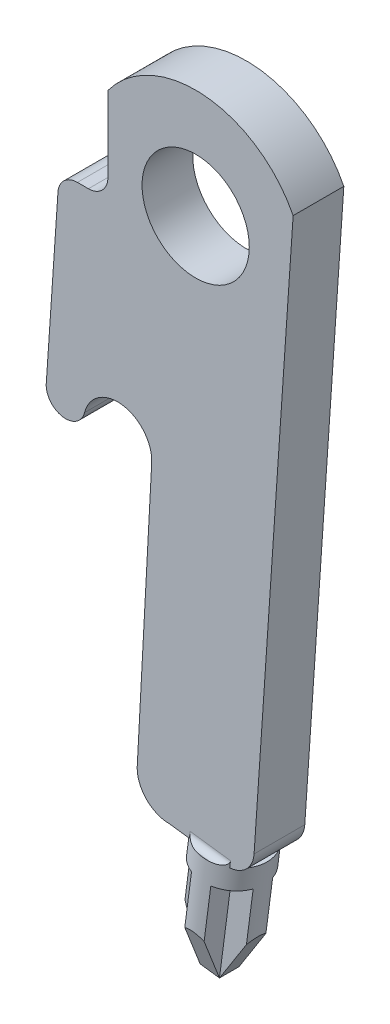
SolidWorks part; units mm, degrees
material "Plain Carbon Steel"
ref_plane "Front Plane" through (0, 0, 0) normal (0, 0, 1) x (1, 0, 0)
ref_plane "Top Plane" through (0, 0, 0) normal (0, 1, 0) x (1, 0, 0)
ref_plane "Right Plane" through (0, 0, 0) normal (1, 0, 0) x (0, 0, -1)
sketch "Sketch1" plane through (0, 0, 0) normal (0, 0, 1) x (1, 0, 0)
  line L0 (16.0633, 36.1424) -> (80.3164, 36.1424) construction
  line L1 (45.7601, 50.3266) -> (45.7601, 46.6183)
  line L2 (45.7601, 46.6183) -> (43.8567, 46.6183)
  line L3 (43.8567, 46.6183) -> (43.3471, 39.1507)
  line L5 (52.9991, 49.7084) -> (51.4727, 27.3397)
  line L6 (47.4717, 38.5713) -> (46.9031, 27.9747)
  line L7 (48.1731, 26.7047) -> (50.1212, 26.4507)
  arc A0 (45.7601, 50.3266) -> (52.9991, 49.7084) centre (49.1891, 47.7867) cw
  arc A1 (43.3471, 39.1507) -> (44.8484, 38.9659) centre (44.1091, 39.1507) ccw
  arc A2 (44.8484, 38.9659) -> (47.4717, 38.5713) centre (46.1411, 38.6427) cw
  circle A5 centre (49.1891, 47.7867) radius 2.0955
  arc A7 (46.9031, 27.9747) -> (48.1731, 26.7047) centre (48.1731, 27.9747) ccw
  arc A8 (51.4727, 27.3397) -> (50.1212, 26.4507) centre (50.4591, 27.4089) cw
  point P10 (0, 0)
  point P19 (42.8058, 39.4047)
  point P22 (0, 0)
  point P23 (44.2839, 38.9493)
  point P24 (0, 0)
  point P25 (0, 0)
  point P26 (44.2626, 39.2936)
  point P27 (0, 0)
  point P28 (0, 0)
  point P29 (44.2905, 39.0006)
  point P30 (49.1891, 47.7867)
  point P31 (0, 0)
  point P32 (0, 0)
  point P33 (0, 0)
  point P34 (0, 0)
  point P35 (0, 0)
  point P36 (0, 0)
  point P37 (0, 0)
  point P38 (0, 0)
  point P39 (0, 0)
  point P40 (0, 0)
  point P41 (0, 0)
  point P42 (0, 0)
  point P43 (0, 0)
  point P44 (0, 0)
  point P45 (0, 0)
  point P46 (0, 0)
  point P47 (0, 0)
  point P48 (0, 0)
  dimension "D1" = 4.191
  dimension "D2" = 4.2672
  dimension "D5" = 8.636
  dimension "D6" = 5.08
  dimension "D8" = 3.048
  dimension "D9" = 0.762
  dimension "D13" = 1.016
  dimension "D17" = 20.447
  dimension "D10" = 19.812
  dimension "D12" = 20.3778
  dimension "D14" = 1.016
  dimension "D15" = 1.27
  dimension "D3" = 1.1684
  dimension "D4" = 3.429
  dimension "D7" = 9.144
  dimension "D11" = 1.27
  dimension "D16" = 21.082
  dimension "D18" = 21.336
extrude "Boss-Extrude1" add sketch "Sketch1" along normal blind 1.9812
fillet "Fillet1" radius 0.762 2 edges at (45.7601, 46.6183, 0.9906) (43.8567, 46.6183, 0.9906)
sketch "Sketch3" plane through (4.2289, 32.4343, 0) normal (-0.1293, -0.9916, 0) x (0.9916, -0.1293, 0)
  line L0 (44.6222, 1.9812) -> (47.1548, 0) construction
  line L1 (47.1548, 1.9812) -> (44.6222, 0) construction
  circle A1 centre (45.8885, 0.9906) radius 1.27
extrude "Boss-Extrude2" add sketch "Sketch3" along normal blind 4.6355
sketch "Sketch5" plane through (3.6296, 27.8377, 0) normal (-0.1293, -0.9916, 0) x (0.9916, -0.1293, 0)
  line L0 (45.8885, 0.9906) -> (45.8885, 2.2606) construction
  line L1 (44.6222, 1.9812) -> (47.1548, 0) construction
  line L2 (45.8885, 0.9906) -> (47.1585, 0.9906) construction
  line L4 (46.2695, 2.2021) -> (47.1, 2.2021)
  line L5 (46.2695, 2.2021) -> (46.2695, 1.3716)
  line L6 (46.2695, 1.3716) -> (47.1, 1.3716)
  line L7 (47.1, 2.2021) -> (47.1, 1.3716)
  circle A0 centre (45.8885, 0.9906) radius 1.27 construction
  arc A1 (47.1585, 0.9906) -> (45.8885, 2.2606) centre (45.8885, 0.9906) ccw
  dimension "D1" = 0.381
  dimension "D2" = 0.381
extrude "Cut-Extrude1" cut sketch "Sketch5" against normal blind 3.81 contours L7 L6 L5 L4
sketch "Sketch6" plane through (45.8812, -5.9821, 0) normal (0.9916, -0.1293, 0) x (0, 0, -1)
  line L0 (-1.3716, 28.0733) -> (-2.2606, 29.9783)
  line L1 (-2.2606, 29.9783) -> (-2.2606, 28.0733)
  line L3 (-2.2606, 28.0733) -> (-1.3716, 28.0733)
  line L4 (-2.2606, 28.0733) -> (0.2794, 28.0733) construction
  line L6 (-2.2606, 32.7088) -> (-2.2606, 28.0733) construction
  dimension "D1" = 1.905
extrude "Cut-Extrude2" cut sketch "Sketch6" against normal blind 3.81
pattern_circular "CirPattern1" count 4 over 360 about axis through (45.5034, -5.9329, 0.9906) along (0.1293, 0.9916, 0) of "Cut-Extrude1", "Cut-Extrude2"
fillet "Fillet3" radius 0.254 2 edges at (49.7322, 26.5014, 1.9812) (49.7322, 26.5014, 0)
